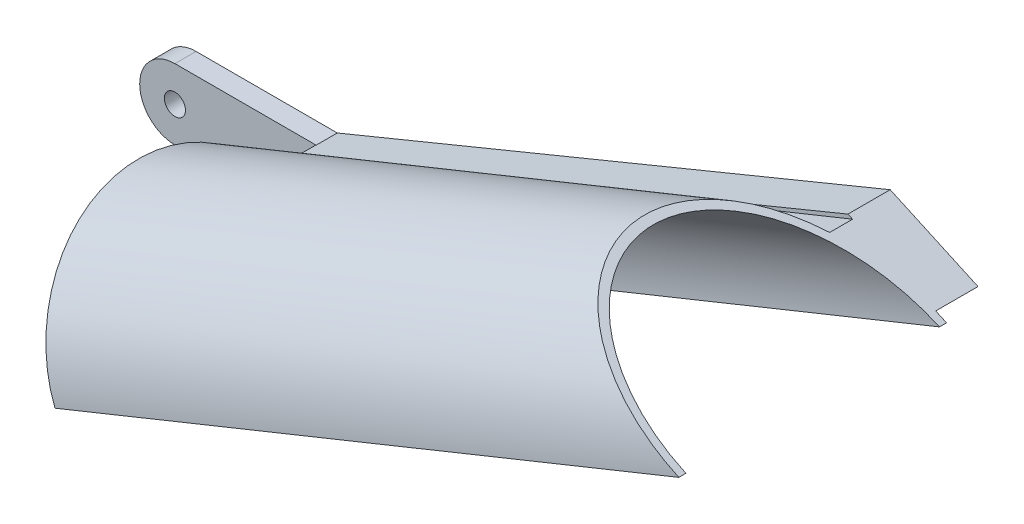
SolidWorks part; units mm, degrees
ref_plane "Front Plane" through (0, 0, 0) normal (0, 0, 1) x (1, 0, 0)
ref_plane "Top Plane" through (0, 0, 0) normal (0, 1, 0) x (1, 0, 0)
ref_plane "Right Plane" through (0, 0, 0) normal (1, 0, 0) x (0, 0, -1)
sketch "Sketch1" plane through (0, 0, 0) normal (0, 0, 1) x (1, 0, 0)
  line L0 (0, 0) -> (22, 0) construction
  line L1 (0, 5) -> (22, 5)
  line L2 (0, -5) -> (22, -5)
  line L3 (21.5213, 1.4216) -> (23.9914, -4.5863) construction
  line L4 (46.409, 15.8375) -> (51.4959, 17.929) construction
  line L5 (20.05, 5) -> (46.409, 15.8375)
  line L6 (51.4959, 17.929) -> (53.6145, 12.7761) construction
  line L7 (53.3599, 12.6714) -> (58.8728, 10.1603)
  line L8 (46.409, 15.8375) -> (53.3599, 12.6714)
  line L9 (48.359, 5.8375) -> (58.8728, 10.1603)
  line L11 (48.359, 5.8375) -> (22, -5)
  arc A0 (0, 5) -> (0, -5) centre (0, 0) ccw
  arc A1 (22, -5) -> (22, 5) centre (22, 0) ccw
  circle A2 centre (0, 0) radius 1.5
  circle A3 centre (22, 0) radius 1.5
  point P3 (11, 0)
  dimension "D2" = 10
  dimension "D11" = 3
  dimension "D1" = 22
  dimension "D3" = 157.65
  dimension "D4" = 1.95
  dimension "D5" = 34
  dimension "D9" = 5.5
extrude "Boss-Extrude1" add sketch "Sketch1" along normal blind 3 contours A1 L1 A0 L2 A3 A2 | A1 L8 L1 region at (10.9566, 0.015, 0) region at (39.2383, 7.2413, 0)
sketch "草图1" plane through (0, 0, 3) normal (0, 0, 1) x (1, 0, 0)
  line L5 (46.409, 15.8375) -> (58.8728, 10.1603)
  line L7 (98.5446, 37.273) -> (111.0084, 31.5958)
  line L8 (46.409, 15.8375) -> (98.5446, 37.273)
  line L17 (58.8728, 10.1603) -> (111.0084, 31.5958)
extrude "凸台-拉伸1" add sketch "草图1" against normal up to surface (3 mm away) up to face at (23.5, 0, 0)
sketch "草图3" plane through (0, 0, 3) normal (0, 0, 1) x (1, 0, 0)
  line L0 (22, 0) -> (0, 0)
  line L1 (0, 0) -> (5.0528, -12.5187)
  line L2 (5.0528, -12.5187) -> (23.9701, -4.8771)
  circle A0 centre (22, 0) radius 5.26
  circle A1 centre (0, 0) radius 13.5
ref_plane "基准面2" through (0, 0, 1.5) normal (0, 0, 1) x (1, 0, 0)
ref_plane "基准面3" through (5.0564, -12.5173, 0) normal (-0.3745, 0.9272, 0) x (0.9272, 0.3745, 0)
ref_plane "基准面4" through (0, 0, 0) normal (0, 0, -1) x (-1, 0, 0)
sketch "草图5" plane through (0, 0, 0) normal (0, 0, -1) x (-1, 0, 0)
  line L0 (-22, 0) -> (-24.655, -6.5727)
ref_plane "基准面5" through (18.9137, 7.6402, 0) normal (0.9272, 0.3745, 0) x (0.3745, -0.9272, 0)
ref_axis "基准轴1" through (23.9701, -4.8771, -9.6126) along (0, 0, 1)
ref_axis "基准轴2" through (30.9339, -22.1164, 0) along (-0.3745, 0.9272, 0)
ref_point "点1"
ref_axis "基准轴3" through (-4.3513, -16.3175, 0) along (0.9272, 0.3745, 0)
sketch "草图17" plane through (0, 0, 3) normal (0, 0, 1) x (1, 0, 0)
  line L0 (111.0084, 31.5958) -> (23.7321, -4.2879)
  line L2 (111.0084, 31.5958) -> (98.5446, 37.273)
  line L3 (98.5446, 37.273) -> (19.9902, 4.9754)
  line L4 (19.9902, 4.9754) -> (21.0636, 2.318)
  line L6 (22.9364, -2.318) -> (23.7321, -4.2879)
  arc A0 (22.9364, -2.318) -> (21.0636, 2.318) centre (22, 0) ccw
extrude "凸台-拉伸3" add sketch "草图17" along normal blind 3
sketch "草图18" plane through (18.9137, 7.6402, 0) normal (0.9272, 0.3745, 0) x (0.3745, -0.9272, 0)
  line L0 (13.5, -6) -> (13.5, -7)
  line L1 (2.874, -6) -> (2.874, -9.2492)
  line L2 (2.874, -6) -> (13.5, -6)
  line L3 (13.5, -43) -> (13.5, -44)
  arc A0 (13.5, -7) -> (13.5, -43) centre (13.5, -25) ccw
  arc A1 (2.874, -9.2492) -> (13.5, -44) centre (13.5, -25) ccw
ref_point "点2"
extrude "凸台-拉伸4" add sketch "草图18" along normal up to surface (95.52 mm away) up to face at (104.7765, 34.4344, 3)
